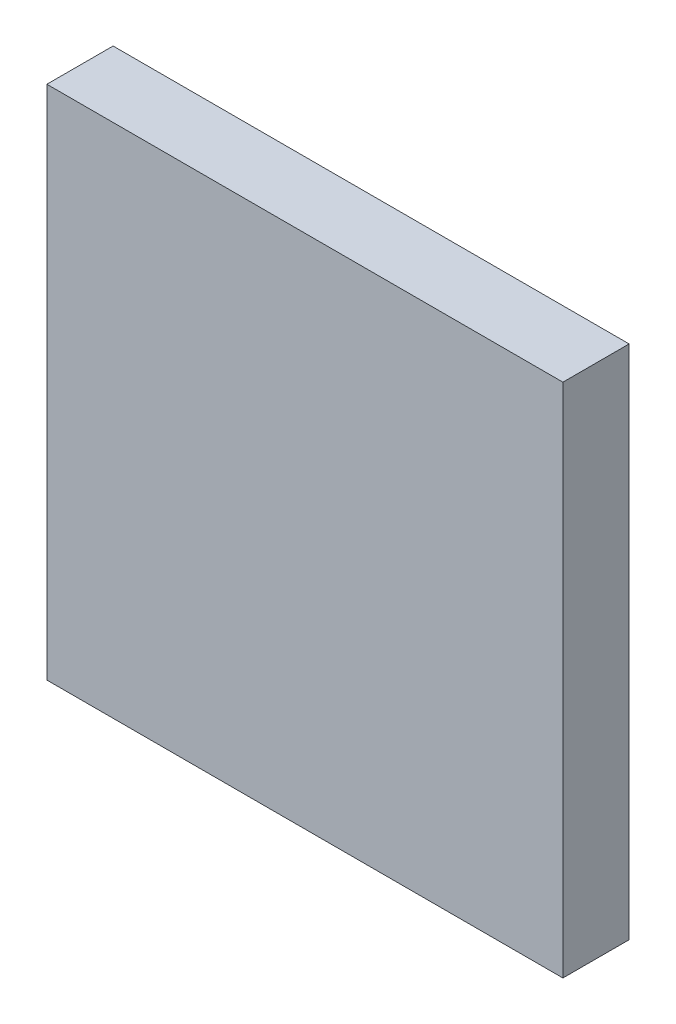
SolidWorks part; units mm, degrees
ref_plane "正面" through (0, 0, 0) normal (0, 0, 1) x (1, 0, 0)
ref_plane "平面" through (0, 0, 0) normal (0, 1, 0) x (1, 0, 0)
ref_plane "右側面" through (0, 0, 0) normal (1, 0, 0) x (0, 0, -1)
sketch "ｽｹｯﾁ1" plane through (0, 0, 0) normal (0, 0, 1) x (1, 0, 0)
  line L0 (-50, 0) -> (50, 0) construction
  line L1 (-50, 50) -> (50, 50)
  line L2 (-50, 50) -> (-50, -50)
  line L3 (-50, -50) -> (50, -50)
  line L4 (50, 50) -> (50, -50)
  line L5 (0, -50) -> (0, 50) construction
  point P8 (0, 0)
  dimension "D1" = 100
  dimension "D2" = 100
  dimension "D3" = 0
  dimension "D4" = 0
extrude "ﾎﾞｽ - 押し出し1" add sketch "ｽｹｯﾁ1" along normal blind 1.6
sketch "ｽｹｯﾁ4" plane through (0, 0, 0) normal (0, 0, -1) x (-1, 0, 0)
  line L0 (-50, -50) -> (-50, 50) construction
  line L1 (11.11, -41.35) -> (28.89, -41.35)
  line L2 (11.11, -41.35) -> (11.11, -43.85)
  line L3 (11.11, -43.85) -> (28.89, -43.85)
  line L4 (28.89, -41.35) -> (28.89, -43.85)
  line L5 (50, -50) -> (-50, -50) construction
  line L6 (50, 50) -> (50, -50) construction
  line L8 (-43.85, -11.11) -> (-41.35, -11.11)
  line L9 (-43.85, -11.11) -> (-43.85, -28.89)
  line L10 (-43.85, -28.89) -> (-41.35, -28.89)
  line L11 (-41.35, -11.11) -> (-41.35, -28.89)
  line L12 (-28.89, 43.85) -> (-11.11, 43.85)
  line L13 (-28.89, 43.85) -> (-28.89, 41.35)
  line L14 (-28.89, 41.35) -> (-11.11, 41.35)
  line L15 (-11.11, 43.85) -> (-11.11, 41.35)
  line L16 (-50, 50) -> (50, 50) construction
  line L18 (41.35, 28.89) -> (43.85, 28.89)
  line L19 (41.35, 28.89) -> (41.35, 11.11)
  line L20 (41.35, 11.11) -> (43.85, 11.11)
  line L21 (43.85, 28.89) -> (43.85, 11.11)
  point P4 (28.89, -42.6)
  point P7 (20, -43.85)
  point P14 (-43.85, -20)
  point P15 (-42.6, -28.89)
  point P22 (-28.89, 42.6)
  point P25 (43.85, 20)
  point P26 (-20, 43.85)
  point P31 (42.6, 28.89)
  dimension "D1" = 7.4
  dimension "D2" = 30
  dimension "D3" = 2.5
  dimension "D4" = 17.78
  dimension "D5" = 2.5
  dimension "D6" = 17.78
  dimension "D7" = 30
  dimension "D8" = 7.4
  dimension "D9" = 2.5
  dimension "D10" = 7.4
  dimension "D11" = 30
  dimension "D12" = 17.78
  dimension "D13" = 17.78
  dimension "D14" = 2.5
  dimension "D15" = 30
  dimension "D16" = 7.4
extrude "ﾎﾞｽ - 押し出し2" add sketch "ｽｹｯﾁ4" along normal blind 2.5
sketch "ｽｹｯﾁ5" plane through (0, 0, -2.5) normal (0, 0, -1) x (-1, 0, 0)
  line L1 (-20.32, 42.92) -> (-19.68, 42.92)
  line L2 (-20.32, 42.92) -> (-20.32, 42.28)
  line L3 (-20.32, 42.28) -> (-19.68, 42.28)
  line L4 (-19.68, 42.92) -> (-19.68, 42.28)
  line L5 (43.85, 28.89) -> (41.35, 28.89) construction
  line L6 (-11.11, 43.85) -> (-28.89, 43.85) construction
  line L7 (-28.89, 43.85) -> (-28.89, 41.35) construction
  line L8 (-43.85, -28.89) -> (-41.35, -28.89) construction
  line L9 (-17.78, 42.92) -> (-17.14, 42.92)
  line L10 (-17.78, 42.92) -> (-17.78, 42.28)
  line L11 (-17.78, 42.28) -> (-17.14, 42.28)
  line L12 (-17.14, 42.92) -> (-17.14, 42.28)
  line L13 (-15.24, 42.92) -> (-14.6, 42.92)
  line L14 (-15.24, 42.92) -> (-15.24, 42.28)
  line L15 (-15.24, 42.28) -> (-14.6, 42.28)
  line L16 (-14.6, 42.92) -> (-14.6, 42.28)
  line L17 (-12.7, 42.92) -> (-12.06, 42.92)
  line L18 (-12.7, 42.92) -> (-12.7, 42.28)
  line L19 (-12.7, 42.28) -> (-12.06, 42.28)
  line L20 (-12.06, 42.92) -> (-12.06, 42.28)
  line L21 (-22.86, 42.92) -> (-22.22, 42.92)
  line L22 (-22.86, 42.92) -> (-22.86, 42.28)
  line L23 (-22.86, 42.28) -> (-22.22, 42.28)
  line L24 (-22.22, 42.92) -> (-22.22, 42.28)
  line L25 (-25.4, 42.92) -> (-24.76, 42.92)
  line L26 (-25.4, 42.92) -> (-25.4, 42.28)
  line L27 (-25.4, 42.28) -> (-24.76, 42.28)
  line L28 (-24.76, 42.92) -> (-24.76, 42.28)
  line L29 (-27.94, 42.92) -> (-27.3, 42.92)
  line L30 (-27.94, 42.92) -> (-27.94, 42.28)
  line L31 (-27.94, 42.28) -> (-27.3, 42.28)
  line L32 (-27.3, 42.92) -> (-27.3, 42.28)
  line L33 (-42.92, -19.68) -> (-42.28, -19.68)
  line L34 (-42.92, -19.68) -> (-42.92, -20.32)
  line L35 (-42.92, -20.32) -> (-42.28, -20.32)
  line L36 (-42.28, -19.68) -> (-42.28, -20.32)
  line L37 (-43.85, -11.11) -> (-43.85, -28.89) construction
  line L38 (43.85, 11.11) -> (43.85, 28.89) construction
  line L39 (-42.92, -22.22) -> (-42.28, -22.22)
  line L40 (-42.92, -22.22) -> (-42.92, -22.86)
  line L41 (-42.92, -22.86) -> (-42.28, -22.86)
  line L42 (-42.28, -22.22) -> (-42.28, -22.86)
  line L44 (42.28, 19.68) -> (42.92, 19.68)
  line L45 (-42.92, -24.76) -> (-42.28, -24.76)
  line L46 (-42.92, -24.76) -> (-42.92, -25.4)
  line L47 (-42.92, -25.4) -> (-42.28, -25.4)
  line L48 (-42.28, -24.76) -> (-42.28, -25.4)
  line L49 (-42.92, -27.3) -> (-42.28, -27.3)
  line L50 (-42.92, -27.3) -> (-42.92, -27.94)
  line L51 (-42.92, -27.94) -> (-42.28, -27.94)
  line L52 (-42.28, -27.3) -> (-42.28, -27.94)
  line L53 (-42.92, -17.14) -> (-42.28, -17.14)
  line L54 (-42.92, -17.14) -> (-42.92, -17.78)
  line L55 (-42.92, -17.78) -> (-42.28, -17.78)
  line L56 (-42.28, -17.14) -> (-42.28, -17.78)
  line L57 (-42.92, -14.6) -> (-42.28, -14.6)
  line L58 (-42.92, -14.6) -> (-42.92, -15.24)
  line L59 (-42.92, -15.24) -> (-42.28, -15.24)
  line L60 (-42.28, -14.6) -> (-42.28, -15.24)
  line L61 (-42.92, -12.06) -> (-42.28, -12.06)
  line L62 (-42.92, -12.06) -> (-42.92, -12.7)
  line L63 (-42.92, -12.7) -> (-42.28, -12.7)
  line L64 (-42.28, -12.06) -> (-42.28, -12.7)
  line L69 (42.28, 19.68) -> (42.28, 20.32)
  line L70 (11.11, -43.85) -> (28.89, -43.85) construction
  line L71 (42.28, 17.78) -> (42.92, 17.78)
  line L72 (42.28, 20.32) -> (42.92, 20.32)
  line L73 (42.92, 19.68) -> (42.92, 20.32)
  line L75 (42.28, 17.78) -> (42.28, 17.14)
  line L76 (42.28, 17.14) -> (42.92, 17.14)
  line L77 (42.92, 17.78) -> (42.92, 17.14)
  line L78 (42.28, 15.24) -> (42.92, 15.24)
  line L79 (42.28, 15.24) -> (42.28, 14.6)
  line L80 (42.28, 14.6) -> (42.92, 14.6)
  line L81 (42.92, 15.24) -> (42.92, 14.6)
  line L82 (42.28, 12.7) -> (42.92, 12.7)
  line L83 (42.28, 12.7) -> (42.28, 12.06)
  line L84 (42.28, 12.06) -> (42.92, 12.06)
  line L85 (42.92, 12.7) -> (42.92, 12.06)
  line L86 (42.28, 22.86) -> (42.92, 22.86)
  line L87 (42.28, 22.86) -> (42.28, 22.22)
  line L88 (42.28, 22.22) -> (42.92, 22.22)
  line L89 (42.92, 22.86) -> (42.92, 22.22)
  line L90 (42.28, 25.4) -> (42.92, 25.4)
  line L91 (42.28, 25.4) -> (42.28, 24.76)
  line L92 (42.28, 24.76) -> (42.92, 24.76)
  line L93 (42.92, 25.4) -> (42.92, 24.76)
  line L94 (42.28, 27.94) -> (42.92, 27.94)
  line L95 (42.28, 27.94) -> (42.28, 27.3)
  line L96 (42.28, 27.3) -> (42.92, 27.3)
  line L97 (42.92, 27.94) -> (42.92, 27.3)
  line L98 (19.68, -42.28) -> (20.32, -42.28)
  line L99 (19.68, -42.28) -> (19.68, -42.92)
  line L100 (19.68, -42.92) -> (20.32, -42.92)
  line L101 (20.32, -42.28) -> (20.32, -42.92)
  line L102 (11.11, -41.35) -> (11.11, -43.85) construction
  line L104 (17.14, -42.28) -> (17.78, -42.28)
  line L105 (17.14, -42.28) -> (17.14, -42.92)
  line L106 (17.14, -42.92) -> (17.78, -42.92)
  line L107 (17.78, -42.28) -> (17.78, -42.92)
  line L108 (14.6, -42.28) -> (15.24, -42.28)
  line L109 (14.6, -42.28) -> (14.6, -42.92)
  line L110 (14.6, -42.92) -> (15.24, -42.92)
  line L111 (15.24, -42.28) -> (15.24, -42.92)
  line L112 (12.06, -42.28) -> (12.7, -42.28)
  line L113 (12.06, -42.28) -> (12.06, -42.92)
  line L114 (12.06, -42.92) -> (12.7, -42.92)
  line L115 (12.7, -42.28) -> (12.7, -42.92)
  line L116 (22.22, -42.28) -> (22.86, -42.28)
  line L117 (22.22, -42.28) -> (22.22, -42.92)
  line L118 (22.22, -42.92) -> (22.86, -42.92)
  line L119 (22.86, -42.28) -> (22.86, -42.92)
  line L120 (24.76, -42.28) -> (25.4, -42.28)
  line L121 (24.76, -42.28) -> (24.76, -42.92)
  line L122 (24.76, -42.92) -> (25.4, -42.92)
  line L123 (25.4, -42.28) -> (25.4, -42.92)
  line L124 (27.3, -42.28) -> (27.94, -42.28)
  line L125 (27.3, -42.28) -> (27.3, -42.92)
  line L126 (27.3, -42.92) -> (27.94, -42.92)
  line L127 (27.94, -42.28) -> (27.94, -42.92)
  point P4 (-20, 42.92)
  point P7 (-20, 43.85)
  point P8 (-20.32, 42.6)
  point P11 (-28.89, 42.6)
  point P16 (-20, 42.28)
  point P17 (-17.46, 42.28)
  point P22 (-14.92, 42.28)
  point P27 (-12.38, 42.28)
  point P40 (-22.54, 42.28)
  point P41 (-25.08, 42.28)
  point P42 (-27.62, 42.28)
  point P47 (-42.6, -20.32)
  point P50 (-42.6, -28.89)
  point P53 (-42.92, -20)
  point P54 (-43.85, -20)
  point P59 (-42.28, -22.54)
  point P60 (-42.28, -20)
  point P61 (-42.28, -25.08)
  point P70 (-42.28, -27.62)
  point P83 (-42.28, -17.46)
  point P84 (-42.28, -14.92)
  point P85 (-42.28, -12.38)
  point P90 (42.6, 19.68)
  point P93 (42.6, 28.89)
  point P94 (42.92, 20)
  point P97 (43.85, 20)
  point P110 (42.28, 12.38)
  point P111 (42.28, 14.92)
  point P112 (42.28, 17.46)
  point P113 (42.28, 20)
  point P126 (42.28, 22.54)
  point P127 (42.28, 25.08)
  point P128 (42.28, 27.62)
  point P133 (20, -42.92)
  point P136 (20, -43.85)
  point P139 (11.11, -42.6)
  point P140 (19.68, -42.6)
  point P165 (17.46, -42.28)
  point P166 (20, -42.28)
  point P167 (14.92, -42.28)
  point P168 (12.38, -42.28)
  point P169 (22.54, -42.28)
  point P170 (25.08, -42.28)
  point P171 (27.62, -42.28)
  point P173 (12.06, -42.6)
  point P174 (14.6, -42.6)
  point P175 (17.14, -42.6)
  point P176 (22.22, -42.6)
  point P177 (24.76, -42.6)
  point P178 (27.3, -42.6)
  point P179 (-42.6, -27.3)
  point P180 (-42.6, -24.76)
  point P181 (-42.6, -22.22)
  point P182 (-42.6, -19.68)
  point P183 (-42.6, -17.14)
  point P184 (-42.6, -14.6)
  point P185 (-42.6, -12.06)
  point P186 (-27.94, 42.6)
  point P187 (-25.4, 42.6)
  point P188 (-22.86, 42.6)
  point P189 (-17.78, 42.6)
  point P190 (-15.24, 42.6)
  point P191 (-12.7, 42.6)
  point P192 (42.6, 15.24)
  point P193 (42.6, 17.78)
  point P194 (42.6, 20.32)
  point P195 (42.6, 22.86)
  point P196 (42.6, 25.4)
  point P197 (42.6, 27.94)
  point P198 (42.6, 12.7)
  dimension "D1" = 0.64
  dimension "D2" = 0.64
  dimension "D3" = 0.64
  dimension "D4" = 0.64
  dimension "D5" = 2.54
  dimension "D6" = 0.64
  dimension "D7" = 2.54
  dimension "D8" = 0.64
  dimension "D9" = 0.64
  dimension "D10" = 0.64
  dimension "D11" = 2.54
  dimension "D12" = 0.64
  dimension "D13" = 0.64
  dimension "D14" = 0.64
  dimension "D15" = 2.54
  dimension "D16" = 0.64
  dimension "D17" = 0.64
  dimension "D18" = 0.64
  dimension "D19" = 2.54
  dimension "D20" = 2.54
  dimension "D21" = 0.64
  dimension "D22" = 0.64
  dimension "D23" = 0.64
  dimension "D24" = 0.64
  dimension "D25" = 2.54
  dimension "D26" = 0.64
  dimension "D27" = 2.54
  dimension "D28" = 0.64
  dimension "D29" = 2.54
  dimension "D30" = 0.64
  dimension "D31" = 0.64
  dimension "D32" = 0.64
  dimension "D33" = 0.64
  dimension "D34" = 2.54
  dimension "D35" = 2.54
  dimension "D36" = 0.64
  dimension "D37" = 0.64
  dimension "D38" = 0.64
  dimension "D39" = 2.54
  dimension "D40" = 0.64
  dimension "D41" = 0.64
  dimension "D42" = 0.64
  dimension "D43" = 0.64
  dimension "D44" = 0.64
  dimension "D45" = 0.64
  dimension "D46" = 2.54
  dimension "D47" = 2.54
  dimension "D48" = 2.54
  dimension "D49" = 2.54
  dimension "D50" = 0.64
  dimension "D51" = 0.64
  dimension "D52" = 0.64
  dimension "D53" = 0.64
  dimension "D54" = 2.54
  dimension "D55" = 0.64
  dimension "D56" = 0.64
  dimension "D57" = 2.54
  dimension "D58" = 0.64
  dimension "D59" = 0.64
  dimension "D60" = 0.64
  dimension "D61" = 0.64
  dimension "D62" = 0.64
  dimension "D63" = 2.54
  dimension "D64" = 2.54
  dimension "D65" = 2.54
  dimension "D66" = 0.64
  dimension "D67" = 0.64
  dimension "D68" = 0.64
  dimension "D69" = 0.64
  dimension "D70" = 0.64
  dimension "D71" = 0.64
  dimension "D72" = 2.54
  dimension "D73" = 2.54
  dimension "D74" = 2.54
  dimension "D75" = 0.64
  dimension "D76" = 0.64
  dimension "D77" = 0.64
  dimension "D78" = 0.64
  dimension "D79" = 0.64
  dimension "D80" = 0.64
extrude "ﾎﾞｽ - 押し出し3" add sketch "ｽｹｯﾁ5" along normal blind 6.1
sketch "ｽｹｯﾁ6" plane through (0, 0, 1.6) normal (0, 0, 1) x (1, 0, 0)
  line L0 (-50, -50) -> (50, -50) construction
  line L1 (-36.74, -33.26) -> (-33.26, -33.26)
  line L2 (-36.74, -33.26) -> (-36.74, -36.74)
  line L3 (-36.74, -36.74) -> (-33.26, -36.74)
  line L4 (-33.26, -33.26) -> (-33.26, -36.74)
  line L5 (-50, 50) -> (-50, -50) construction
  line L6 (50, 50) -> (-50, 50) construction
  line L7 (-36.74, 36.74) -> (-33.26, 36.74)
  line L8 (-36.74, 36.74) -> (-36.74, 33.26)
  line L9 (-36.74, 33.26) -> (-33.26, 33.26)
  line L10 (-33.26, 36.74) -> (-33.26, 33.26)
  line L11 (50, -50) -> (50, 50) construction
  line L12 (33.26, -33.26) -> (36.74, -33.26)
  line L13 (33.26, -33.26) -> (33.26, -36.74)
  line L14 (33.26, -36.74) -> (36.74, -36.74)
  line L15 (36.74, -33.26) -> (36.74, -36.74)
  line L17 (33.26, 36.74) -> (36.74, 36.74)
  line L18 (33.26, 36.74) -> (33.26, 33.26)
  line L19 (33.26, 33.26) -> (36.74, 33.26)
  line L20 (36.74, 36.74) -> (36.74, 33.26)
  point P4 (-36.74, -35)
  point P7 (-35, -36.74)
  point P14 (-36.74, 35)
  point P17 (-35, 36.74)
  point P22 (35, -36.74)
  point P25 (36.74, -35)
  point P30 (35, 36.74)
  point P31 (36.74, 35)
  dimension "D1" = 3.48
  dimension "D2" = 3.48
  dimension "D3" = 15
  dimension "D4" = 15
  dimension "D5" = 3.48
  dimension "D6" = 3.48
  dimension "D7" = 15
  dimension "D8" = 15
  dimension "D9" = 15
  dimension "D10" = 15
  dimension "D11" = 3.48
  dimension "D12" = 3.48
  dimension "D13" = 15
  dimension "D14" = 15
  dimension "D15" = 3.48
  dimension "D16" = 3.48
extrude "ﾎﾞｽ - 押し出し4" add sketch "ｽｹｯﾁ6" along normal blind 2
sketch "ｽｹｯﾁ7" plane through (0, 0, 1.6) normal (0, 0, 1) x (1, 0, 0)
  line L0 (-50, -50) -> (50, -50) construction
  line L1 (-38.5, 2) -> (-36.5, 2)
  line L2 (-38.5, 2) -> (-38.5, -2)
  line L3 (-38.5, -2) -> (-36.5, -2)
  line L4 (-36.5, 2) -> (-36.5, -2)
  line L5 (-50, 50) -> (-50, -50) construction
  line L6 (50, -50) -> (50, 50) construction
  line L7 (36.5, 2) -> (38.5, 2)
  line L8 (36.5, 2) -> (36.5, -2)
  line L9 (36.5, -2) -> (38.5, -2)
  line L10 (38.5, 2) -> (38.5, -2)
  line L11 (50, 50) -> (-50, 50) construction
  line L12 (-2, 38.5) -> (2, 38.5)
  line L13 (-2, 38.5) -> (-2, 36.5)
  line L14 (-2, 36.5) -> (2, 36.5)
  line L15 (2, 38.5) -> (2, 36.5)
  line L17 (-2, -36.5) -> (2, -36.5)
  line L18 (-2, -36.5) -> (-2, -38.5)
  line L19 (-2, -38.5) -> (2, -38.5)
  line L20 (2, -36.5) -> (2, -38.5)
  line L21 (-1, 2) -> (1, 2)
  line L22 (-1, 2) -> (-1, -2)
  line L23 (-1, -2) -> (1, -2)
  line L24 (1, 2) -> (1, -2)
  point P4 (-38.5, 0)
  point P7 (-37.5, -2)
  point P14 (37.5, 2)
  point P17 (38.5, 0)
  point P22 (-2, 37.5)
  point P25 (0, 38.5)
  point P30 (-2, -37.5)
  point P31 (0, -38.5)
  point P36 (1, 0)
  point P37 (36.5, 0)
  point P38 (0, 36.5)
  point P39 (0, 2)
  dimension "D1" = 4
  dimension "D2" = 2
  dimension "D3" = 50
  dimension "D4" = 12.5
  dimension "D5" = 4
  dimension "D6" = 2
  dimension "D7" = 12.5
  dimension "D8" = 50
  dimension "D9" = 4
  dimension "D10" = 2
  dimension "D11" = 12.5
  dimension "D12" = 50
  dimension "D13" = 4
  dimension "D14" = 2
  dimension "D15" = 12.5
  dimension "D16" = 50
  dimension "D17" = 4
  dimension "D18" = 2
extrude "ﾎﾞｽ - 押し出し5" add sketch "ｽｹｯﾁ7" along normal blind 1.1
sketch "ｽｹｯﾁ8" plane through (0, 0, 1.6) normal (0, 0, 1) x (1, 0, 0)
  line L0 (-50, -50) -> (50, -50) construction
  line L1 (-7.6, -13.3) -> (7.6, -13.3)
  line L2 (-7.6, -13.3) -> (-7.6, -20.7)
  line L3 (-7.6, -20.7) -> (7.6, -20.7)
  line L4 (7.6, -13.3) -> (7.6, -20.7)
  point P4 (-7.6, -17)
  point P7 (0, -50)
  point P8 (0, -20.7)
  dimension "D1" = 7.4
  dimension "D2" = 15.2
  dimension "D3" = 33
extrude "ﾎﾞｽ - 押し出し6" add sketch "ｽｹｯﾁ8" along normal blind 2.65
sketch "ｽｹｯﾁ9" plane through (0, 0, 0) normal (0, 0, -1) x (-1, 0, 0)
  line L1 (-4.61, 19.83) -> (3.01, 19.83)
  line L2 (-4.61, 19.83) -> (-4.61, 17.33)
  line L3 (-4.61, 17.33) -> (3.01, 17.33)
  line L4 (3.01, 19.83) -> (3.01, 17.33)
  line L5 (50, 50) -> (50, -50) construction
  line L6 (50, -50) -> (-50, -50) construction
  point P4 (-0.8, 19.83)
  point P7 (3.01, 18.58)
  dimension "D1" = 7.62
  dimension "D2" = 2.5
  dimension "D3" = 50.8
  dimension "D4" = 68.58
extrude "ﾎﾞｽ - 押し出し7" add sketch "ｽｹｯﾁ9" along normal blind 2.5
sketch "ｽｹｯﾁ11" plane through (0, 0, -2.5) normal (0, 0, -1) x (-1, 0, 0)
  line L0 (3.01, 19.83) -> (-4.61, 19.83) construction
  line L1 (-1.12, 18.9) -> (-0.48, 18.9)
  line L2 (-1.12, 18.9) -> (-1.12, 18.26)
  line L3 (-1.12, 18.26) -> (-0.48, 18.26)
  line L4 (-0.48, 18.9) -> (-0.48, 18.26)
  line L5 (-4.61, 19.83) -> (-4.61, 17.33) construction
  line L7 (-3.66, 18.9) -> (-3.02, 18.9)
  line L8 (-3.66, 18.9) -> (-3.66, 18.26)
  line L9 (-3.66, 18.26) -> (-3.02, 18.26)
  line L10 (-3.02, 18.9) -> (-3.02, 18.26)
  line L11 (1.42, 18.9) -> (2.06, 18.9)
  line L12 (1.42, 18.9) -> (1.42, 18.26)
  line L13 (1.42, 18.26) -> (2.06, 18.26)
  line L14 (2.06, 18.9) -> (2.06, 18.26)
  point P4 (-0.8, 18.9)
  point P7 (-0.8, 19.83)
  point P8 (-1.12, 18.58)
  point P11 (-4.61, 18.58)
  point P20 (-3.34, 18.26)
  point P21 (-0.8, 18.26)
  point P22 (1.74, 18.26)
  point P23 (-3.66, 18.58)
  point P25 (1.42, 18.58)
  dimension "D1" = 0.64
  dimension "D2" = 0.64
  dimension "D3" = 0.64
  dimension "D4" = 0.64
  dimension "D5" = 0.64
  dimension "D6" = 2.54
  dimension "D7" = 2.54
extrude "ﾎﾞｽ - 押し出し8" add sketch "ｽｹｯﾁ11" along normal blind 6.1
sketch "ｽｹｯﾁ13" plane through (0, 0, 0) normal (0, 0, -1) x (-1, 0, 0)
  line L0 (-50, -50) -> (-50, 50) construction
  line L7 (-50, 50) -> (50, 50) construction
  line L8 (50, -50) -> (-50, -50) construction
  line L15 (50, 50) -> (50, -50) construction
  line L23 (32, -30) -> (31, -28.2679)
  line L24 (31, -28.2679) -> (29, -28.2679)
  line L25 (29, -28.2679) -> (28, -30)
  line L26 (28, -30) -> (29, -31.7321)
  line L27 (29, -31.7321) -> (31, -31.7321)
  line L28 (31, -31.7321) -> (32, -30)
  line L29 (-28, -30) -> (-29, -28.2679)
  line L30 (-29, -28.2679) -> (-31, -28.2679)
  line L31 (-31, -28.2679) -> (-32, -30)
  line L32 (-32, -30) -> (-31, -31.7321)
  line L33 (-31, -31.7321) -> (-29, -31.7321)
  line L34 (-29, -31.7321) -> (-28, -30)
  line L35 (32, 30) -> (31, 31.7321)
  line L36 (31, 31.7321) -> (29, 31.7321)
  line L37 (29, 31.7321) -> (28, 30)
  line L38 (28, 30) -> (29, 28.2679)
  line L39 (29, 28.2679) -> (31, 28.2679)
  line L40 (31, 28.2679) -> (32, 30)
  line L41 (-28, 30) -> (-29, 31.7321)
  line L42 (-29, 31.7321) -> (-31, 31.7321)
  line L43 (-31, 31.7321) -> (-32, 30)
  line L44 (-32, 30) -> (-31, 28.2679)
  line L45 (-31, 28.2679) -> (-29, 28.2679)
  line L46 (-29, 28.2679) -> (-28, 30)
  circle A0 centre (-30, 30) radius 2 construction
  circle A1 centre (-30, -30) radius 2 construction
  circle A2 centre (30, 30) radius 2 construction
  circle A3 centre (30, -30) radius 2 construction
  dimension "D1" = 20
  dimension "D2" = 20
  dimension "D3" = 20
  dimension "D4" = 20
  dimension "D5" = 20
  dimension "D6" = 20
  dimension "D7" = 20
  dimension "D8" = 20
extrude "ﾎﾞｽ - 押し出し9" add sketch "ｽｹｯﾁ13" along normal blind 6
sketch "ｽｹｯﾁ14" plane through (0, 0, -6) normal (0, 0, -1) x (-1, 0, 0)
  line L2 (0, -39) -> (0, -41)
  line L3 (0, -41) -> (39, -41)
  line L4 (39, -41) -> (39, 0)
  line L5 (39, 0) -> (41, 0)
  line L6 (41, 0) -> (41, 39)
  line L7 (41, 39) -> (0, 39)
  line L8 (0, 39) -> (0, 41)
  line L9 (0, 41) -> (-39, 41)
  line L11 (-39, 41) -> (-39, 0)
  line L12 (-39, 0) -> (-41, 0)
  line L13 (-41, 0) -> (-41, -39)
  line L14 (-41, -39) -> (0, -39)
  line L21 (-29, 31.7321) -> (-31, 31.7321) construction
  line L22 (-4.61, 19.83) -> (3.01, 19.83)
  line L23 (-4.61, 19.83) -> (-4.61, 17.33)
  line L24 (-4.61, 17.33) -> (3.01, 17.33)
  line L25 (3.01, 19.83) -> (3.01, 17.33)
  line L26 (31, 31.7321) -> (29, 31.7321) construction
  line L27 (31, -28.2679) -> (29, -28.2679) construction
  line L28 (-29, -28.2679) -> (-31, -28.2679) construction
  circle A0 centre (-30, 30) radius 1
  circle A1 centre (30, 30) radius 1
  circle A2 centre (30, -30) radius 1
  circle A3 centre (-30, -30) radius 1
  point P28 (-30, 31.7321)
  point P37 (30, 31.7321)
  point P41 (30, -28.2679)
  point P47 (-30, -28.2679)
  dimension "D1" = 39
  dimension "D2" = 41
  dimension "D3" = 41
  dimension "D4" = 39
  dimension "D5" = 41
  dimension "D6" = 39
  dimension "D7" = 41
  dimension "D8" = 39
  dimension "D9" = 2.5
  dimension "D10" = 7.62
extrude "ﾎﾞｽ - 押し出し10" add sketch "ｽｹｯﾁ14" along normal blind 2 separate body
sketch "ｽｹｯﾁ15" plane through (0, 0, -2.5) normal (0, 0, -1) x (-1, 0, 0)
  line L1 (-60, 60) -> (60, 60)
  line L2 (-60, 60) -> (-60, -60)
  line L3 (-60, -60) -> (60, -60)
  line L4 (60, 60) -> (60, -60)
  point P4 (0, 60)
  point P6 (-60, 0)
  dimension "D1" = 120
  dimension "D2" = 120
extrude "ﾎﾞｽ - 押し出し11" add sketch "ｽｹｯﾁ15" against normal blind 15.4 separate body
